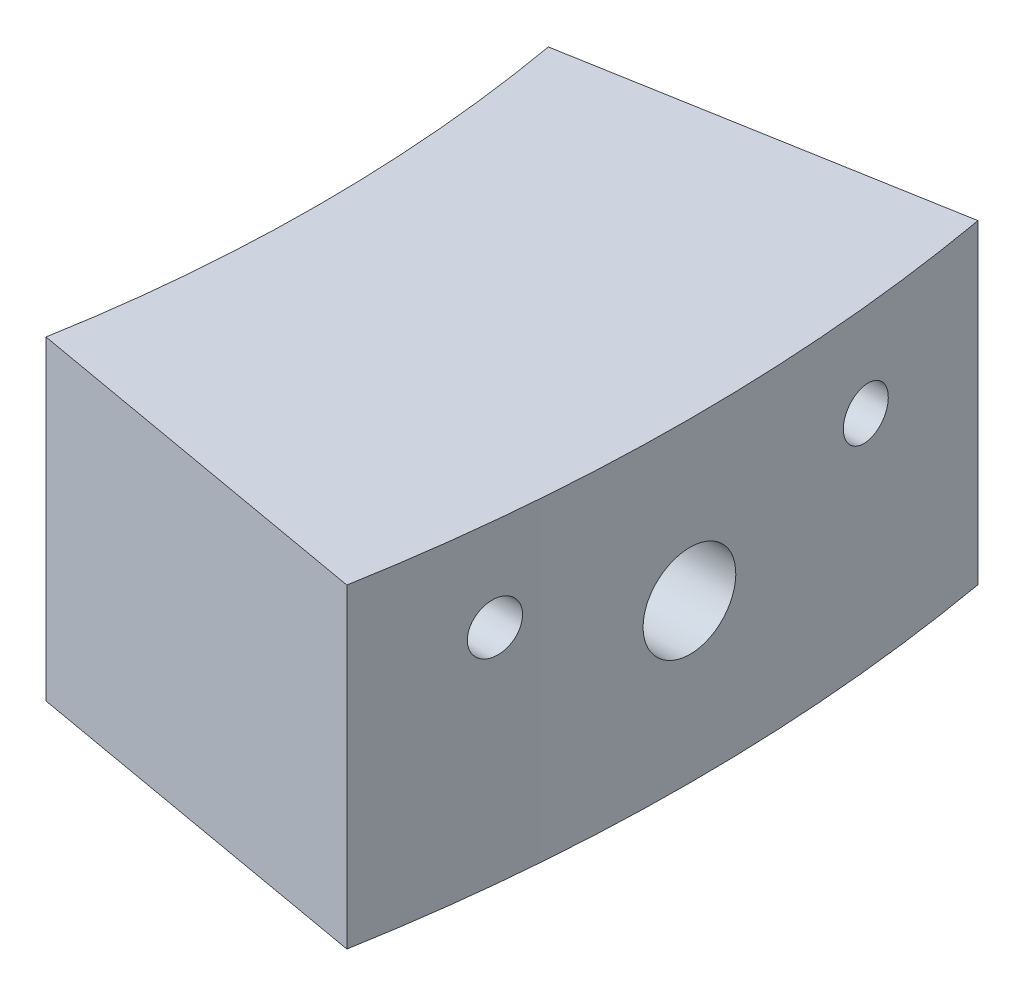
SolidWorks part; units mm, degrees
ref_plane "Front Plane" through (0, 0, 0) normal (0, 0, 1) x (1, 0, 0)
ref_plane "Top Plane" through (0, 0, 0) normal (0, 1, 0) x (1, 0, 0)
ref_plane "Right Plane" through (0, 0, 0) normal (1, 0, 0) x (0, 0, -1)
ref_axis "Axis1" through (0, -55, 0) along (0, 1, 0)
ref_axis "Axis2" through (0, 0, 71.2617) along (0, 0, -1)
ref_plane "Plane1" through (80, 0, 0) normal (1, 0, 0) x (0, 0, -1)
sketch "Sketch1" plane through (0, 0, 0) normal (0, 0, 1) x (1, 0, 0)
  line L0 (78, 17) -> (78, 0)
  line L1 (78, 0) -> (98, 0)
  line L2 (98, 17) -> (98, 0)
  line L3 (78, 17) -> (98, 17)
  line L4 (0, -55) -> (0, 55) construction
  dimension "D1" = 78
  dimension "D2" = 17
  dimension "D3" = 20
revolve "Revolve1" add sketch "Sketch1" angle 20 mid plane about axis through (0, -55, 0) along (0, 1, 0)
sketch "Sketch2" plane through (80, 0, 0) normal (1, 0, 0) x (0, 0, -1)
  line L0 (0, -55) -> (0, 55) construction
  line L1 (-71.2617, 0) -> (71.2617, 0) construction
  line L2 (13.5446, 17) -> (-13.5446, 17) construction
  circle A0 centre (0, 8.5) radius 2.5
  circle A1 centre (-10, 12) radius 1.35
  circle A2 centre (10, 12) radius 1.35
  point P10 (0, 0)
  point P11 (0, 12)
  point P12 (9.3966, 11.921)
  point P13 (0, 0)
  point P14 (0, 0)
  point P15 (-9.4018, 11.921)
  point P16 (0, 0)
  dimension "D1" = 5
  dimension "D5" = 2.7
  dimension "D2" = 8.5
  dimension "D3" = 10
  dimension "D4" = 10
  dimension "D6" = 5
extrude "Cut-Extrude1" cut sketch "Sketch2" along normal blind 20
